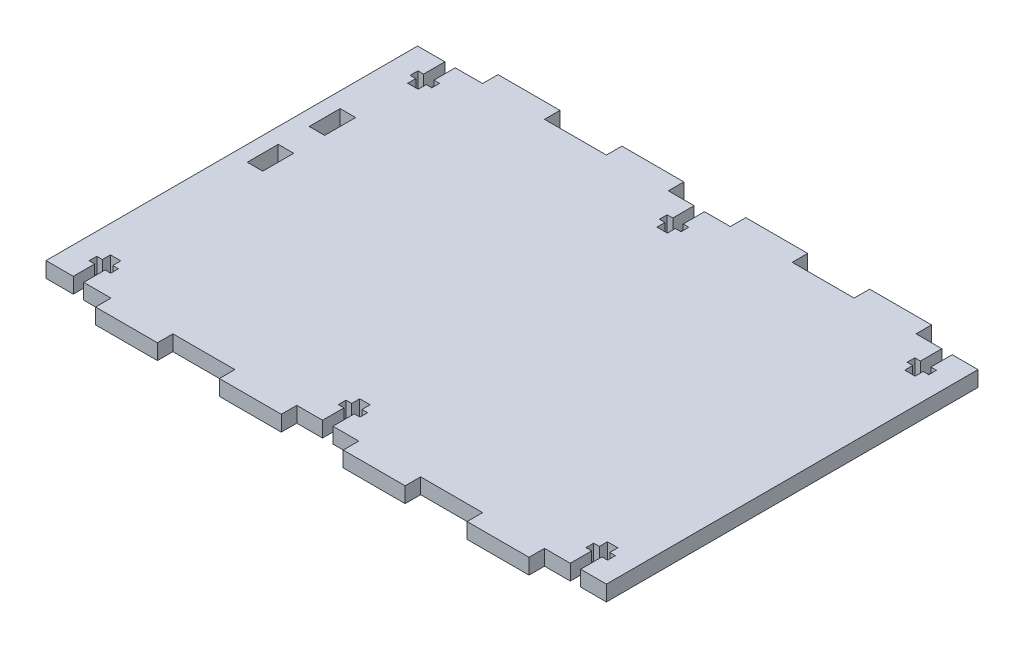
SolidWorks part; units mm, degrees
ref_plane "Front Plane" through (0, 0, 0) normal (0, 0, 1) x (1, 0, 0)
ref_plane "Top Plane" through (0, 0, 0) normal (0, 1, 0) x (1, 0, 0)
ref_plane "Right Plane" through (0, 0, 0) normal (1, 0, 0) x (0, 0, -1)
sketch "Sketch1" plane through (0, 0, 0) normal (0, 0, 1) x (1, 0, 0)
  line L0 (90.51, -15.875) -> (90.51, 155.575) construction
  line L1 (-139.3499, 155.575) -> (90.51, 155.575)
  line L2 (-139.3499, 155.575) -> (-139.3499, 149.225)
  line L3 (-139.3499, 149.225) -> (90.51, 149.225)
  line L4 (90.51, 155.575) -> (90.51, 149.225)
  dimension "D1" = 6.35
extrude "Boss-Extrude1" add sketch "Sketch1" along normal blind 152.4
sketch "Sketch2" plane through (0, 155.575, 0) normal (0, 1, 0) x (1, 0, 0)
  line L0 (65.11, 0) -> (65.11, 6.35)
  line L1 (90.51, 0) -> (-139.3499, 0) construction
  line L2 (-139.3499, 6.35) -> (-112.69, 6.35) construction
  line L3 (65.11, 6.35) -> (39.71, 6.35)
  line L4 (39.71, 6.35) -> (39.71, 0)
  line L5 (90.51, 0) -> (65.11, 0)
  line L6 (65.11, 0) -> (39.71, 0)
  line L9 (90.51, 0) -> (-139.3499, 0)
  line L10 (-139.3499, 0) -> (-139.3499, -152.4)
  line L11 (-139.3499, -152.4) -> (90.51, -152.4)
  line L12 (90.51, -152.4) -> (90.51, 0)
  line L13 (39.71, 0) -> (-139.3499, 0)
  line L14 (-139.3499, 0) -> (-139.3499, -152.4)
  line L15 (-139.3499, -152.4) -> (90.51, -152.4)
  line L16 (90.51, -152.4) -> (90.51, 0)
  line M7 (90.51, 0) -> (-139.3499, 0)
  dimension "D1" = 25.4
  dimension "D2" = 25.4
  dimension "D3" = 0
extrude "Boss-Extrude2" add sketch "Sketch2" against normal blind 6.35 contours L3 L4 L0 M7 region at (52.41, 155.575, -3.175)
pattern_linear "LPattern1" count 4 spacing 50.8 along (-1, 0, 0) of "Boss-Extrude2"
sketch "Sketch3" plane through (0, 0, 152.4) normal (0, 0, 1) x (1, 0, 0)
  line L0 (90.51, 155.575) -> (-139.3499, 155.575) construction
  line L1 (65.11, 155.575) -> (39.71, 155.575)
  line L2 (65.11, 155.575) -> (65.11, 149.225)
  line L3 (65.11, 149.225) -> (39.71, 149.225)
  line L4 (39.71, 155.575) -> (39.71, 149.225)
  line L5 (-139.3499, 149.225) -> (90.51, 149.225) construction
  dimension "D1" = 25.4
  dimension "D2" = 25.4
extrude "Boss-Extrude3" add sketch "Sketch3" along normal blind 6.35
pattern_linear "LPattern2" count 4 spacing 50.8 along (-1, 0, 0) of "Boss-Extrude3"
sketch "Sketch4" plane through (0, 155.575, 0) normal (0, 1, 0) x (1, 0, 0)
  line L0 (-139.3499, 0) -> (-112.69, 0) construction
  line L1 (65.11, 0) -> (90.51, 0) construction
  line L2 (-126.0199, 0) -> (-126.0199, -13.6148) construction
  line L3 (-112.69, 0) -> (-139.3499, 0) construction
  line L4 (-23.79, 0) -> (-23.79, -16.5479) construction
  line L5 (-11.09, 0) -> (-36.49, 0) construction
  line L6 (77.81, 0) -> (77.81, -21.5198) construction
  line L7 (90.51, 0) -> (65.11, 0) construction
  line L8 (77.81, -152.4) -> (77.81, -137.4626) construction
  line L9 (90.51, -152.4) -> (65.11, -152.4) construction
  line L10 (-23.79, -152.4) -> (-23.79, -137.4626) construction
  line L11 (-11.09, -152.4) -> (-36.49, -152.4) construction
  line L12 (-126.0199, -152.4) -> (-126.0199, -137.4626) construction
  line L13 (-112.69, -152.4) -> (-139.3499, -152.4) construction
  line L14 (-139.3499, -152.4) -> (-112.69, -152.4) construction
  line L15 (-36.49, -152.4) -> (-11.09, -152.4) construction
  line B0 (-123.8863, 0) -> (-128.1535, 0)
  line B1 (-128.1535, -11.938) -> (-130.4649, -11.938)
  line B2 (-130.4649, -11.938) -> (-130.4649, -8.763)
  line B3 (-130.4649, -8.763) -> (-128.1535, -8.763)
  line B4 (-128.1535, -8.763) -> (-128.1535, 0)
  line B5 (-128.1535, -11.938) -> (-128.1535, -15.24)
  line B6 (-128.1535, -15.24) -> (-123.8863, -15.24)
  line B7 (-123.8863, -11.938) -> (-123.8863, -15.24)
  line B8 (-123.8863, -8.763) -> (-123.8863, 0)
  line B9 (-121.5749, -8.763) -> (-123.8863, -8.763)
  line B10 (-121.5749, -11.938) -> (-121.5749, -8.763)
  line B11 (-123.8863, -11.938) -> (-121.5749, -11.938)
  line B12 (-21.6564, 0) -> (-25.9236, 0)
  line B13 (-25.9236, -11.938) -> (-28.235, -11.938)
  line B14 (-28.235, -11.938) -> (-28.235, -8.763)
  line B15 (-28.235, -8.763) -> (-25.9236, -8.763)
  line B16 (-25.9236, -8.763) -> (-25.9236, 0)
  line B17 (-25.9236, -11.938) -> (-25.9236, -15.24)
  line B18 (-25.9236, -15.24) -> (-21.6564, -15.24)
  line B19 (-21.6564, -11.938) -> (-21.6564, -15.24)
  line B20 (-21.6564, -8.763) -> (-21.6564, 0)
  line B21 (-19.345, -8.763) -> (-21.6564, -8.763)
  line B22 (-19.345, -11.938) -> (-19.345, -8.763)
  line B23 (-21.6564, -11.938) -> (-19.345, -11.938)
  line B24 (79.9436, 0) -> (75.6764, 0)
  line B25 (75.6764, -11.938) -> (73.365, -11.938)
  line B26 (73.365, -11.938) -> (73.365, -8.763)
  line B27 (73.365, -8.763) -> (75.6764, -8.763)
  line B28 (75.6764, -8.763) -> (75.6764, 0)
  line B29 (75.6764, -11.938) -> (75.6764, -15.24)
  line B30 (75.6764, -15.24) -> (79.9436, -15.24)
  line B31 (79.9436, -11.938) -> (79.9436, -15.24)
  line B32 (79.9436, -8.763) -> (79.9436, 0)
  line B33 (82.255, -8.763) -> (79.9436, -8.763)
  line B34 (82.255, -11.938) -> (82.255, -8.763)
  line B35 (79.9436, -11.938) -> (82.255, -11.938)
  line B36 (-128.1535, -152.4) -> (-123.8863, -152.4)
  line B37 (-123.8863, -140.462) -> (-121.5749, -140.462)
  line B38 (-121.5749, -140.462) -> (-121.5749, -143.637)
  line B39 (-121.5749, -143.637) -> (-123.8863, -143.637)
  line B40 (-123.8863, -143.637) -> (-123.8863, -152.4)
  line B41 (-123.8863, -140.462) -> (-123.8863, -137.16)
  line B42 (-123.8863, -137.16) -> (-128.1535, -137.16)
  line B43 (-128.1535, -140.462) -> (-128.1535, -137.16)
  line B44 (-128.1535, -143.637) -> (-128.1535, -152.4)
  line B45 (-130.4649, -143.637) -> (-128.1535, -143.637)
  line B46 (-130.4649, -140.462) -> (-130.4649, -143.637)
  line B47 (-128.1535, -140.462) -> (-130.4649, -140.462)
  line B48 (-25.9236, -152.4) -> (-21.6564, -152.4)
  line B49 (-21.6564, -140.462) -> (-19.345, -140.462)
  line B50 (-19.345, -140.462) -> (-19.345, -143.637)
  line B51 (-19.345, -143.637) -> (-21.6564, -143.637)
  line B52 (-21.6564, -143.637) -> (-21.6564, -152.4)
  line B53 (-21.6564, -140.462) -> (-21.6564, -137.16)
  line B54 (-21.6564, -137.16) -> (-25.9236, -137.16)
  line B55 (-25.9236, -140.462) -> (-25.9236, -137.16)
  line B56 (-25.9236, -143.637) -> (-25.9236, -152.4)
  line B57 (-28.235, -143.637) -> (-25.9236, -143.637)
  line B58 (-28.235, -140.462) -> (-28.235, -143.637)
  line B59 (-25.9236, -140.462) -> (-28.235, -140.462)
  line B60 (75.6764, -152.4) -> (79.9436, -152.4)
  line B61 (79.9436, -140.462) -> (82.255, -140.462)
  line B62 (82.255, -140.462) -> (82.255, -143.637)
  line B63 (82.255, -143.637) -> (79.9436, -143.637)
  line B64 (79.9436, -143.637) -> (79.9436, -152.4)
  line B65 (79.9436, -140.462) -> (79.9436, -137.16)
  line B66 (79.9436, -137.16) -> (75.6764, -137.16)
  line B67 (75.6764, -140.462) -> (75.6764, -137.16)
  line B68 (75.6764, -143.637) -> (75.6764, -152.4)
  line B69 (73.365, -143.637) -> (75.6764, -143.637)
  line B70 (73.365, -140.462) -> (73.365, -143.637)
  line B71 (75.6764, -140.462) -> (73.365, -140.462)
sketch_block_instance "TSlot-1"
sketch_block "TSlot" parameters "D1"=3.302, "D2"=3.175
sketch_block_instance "TSlot-3"
sketch_block_instance "TSlot-4"
sketch_block_instance "TSlot-9"
sketch_block_instance "TSlot-11"
sketch_block_instance "TSlot-12"
extrude "Cut-Extrude1" cut sketch "Sketch4" against normal blind 6.35
sketch "Sketch5" plane through (0, 155.575, 0) normal (0, 1, 0) x (1, 0, 0)
  line L0 (-132.9999, -55.2358) -> (-132.9999, -140.7347) construction
  line L1 (-132.9999, -38.1) -> (-126.6499, -38.1)
  line L2 (-132.9999, -38.1) -> (-132.9999, -50.8)
  line L3 (-132.9999, -50.8) -> (-126.6499, -50.8)
  line L4 (-126.6499, -38.1) -> (-126.6499, -50.8)
  line L5 (-132.9999, -63.5) -> (-126.6499, -63.5)
  line L6 (-132.9999, -63.5) -> (-132.9999, -76.2)
  line L7 (-132.9999, -76.2) -> (-126.6499, -76.2)
  line L8 (-126.6499, -63.5) -> (-126.6499, -76.2)
  line L10 (-139.3499, -152.4) -> (-139.3499, 0) construction
  line L11 (-128.1535, 0) -> (-139.3499, 0) construction
  dimension "D1" = 12.7
  dimension "D2" = 6.35
  dimension "D3" = 6.35
  dimension "D4" = 12.7
  dimension "D5" = 12.7
  dimension "D6" = 6.35
  dimension "D7" = 38.1
extrude "Cut-Extrude2" cut sketch "Sketch5" against normal through all
